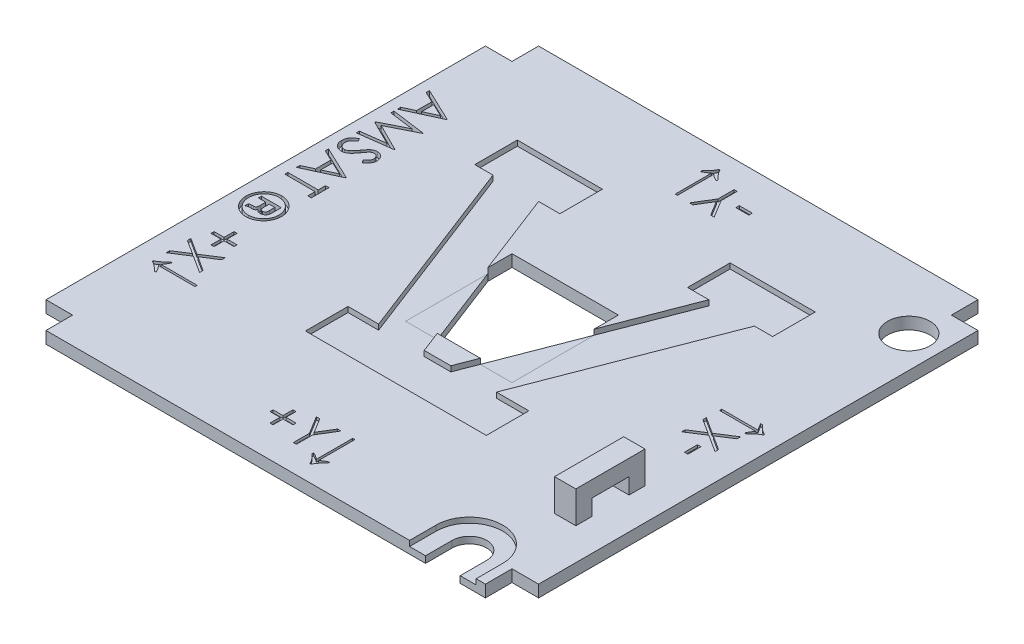
SolidWorks part; units mm, degrees
ref_plane "Front" through (0, 0, 0) normal (0, 0, 1) x (1, 0, 0)
ref_plane "Top" through (0, 0, 0) normal (0, 1, 0) x (1, 0, 0)
ref_plane "Right" through (0, 0, 0) normal (1, 0, 0) x (0, 0, -1)
sketch "Sketch2" plane through (0, 0, 0) normal (0, 1, 0) x (1, 0, 0)
  line L1 (-46.3, 41.3) -> (46.3, 41.3)
  line L2 (-46.3, 41.3) -> (-46.3, -41.3)
  line L3 (-46.3, -41.3) -> (46.3, -41.3)
  line L4 (46.3, 41.3) -> (46.3, -41.3)
  line L5 (-46.3, 41.3) -> (46.3, -41.3) construction
  line L6 (-46.3, -41.3) -> (46.3, 41.3) construction
  line L7 (-41.3, 46.3) -> (41.3, 46.3)
  line L8 (-41.3, 46.3) -> (-41.3, -46.3)
  line L9 (-41.3, -46.3) -> (41.3, -46.3)
  line L10 (41.3, 46.3) -> (41.3, -46.3)
  line L11 (-41.3, 46.3) -> (41.3, -46.3) construction
  line L12 (-41.3, -46.3) -> (41.3, 46.3) construction
  point P0 (0, 0)
  point P6 (0, 0)
  dimension "D1" = 82.6
  dimension "D2" = 92.6
  dimension "D3" = 92.6
  dimension "D4" = 82.6
extrude "Boss-Extrude1" add sketch "Sketch2" along normal blind 2.25 contours L8 L1 L2 L3 | L10 L1 L8 L3 | L10 L3 L8 L9 | L1 L10 L3 L4 | L10 L7 L8 L1 region at (-43.8, 0, 0) region at (0, 0, -43.8) region at (0, 0, 0) region at (43.8, 0, 0) region at (0, 0, 43.8)
sketch "Sketch4" plane through (0, 2.25, 0) normal (0, 1, 0) x (1, 0, 0)
  line L1 (-38.2288, 21.7712) -> (-18.2288, 21.7712)
  line L2 (-38.2288, 21.7712) -> (-38.2288, -8.2288)
  line L3 (-38.2288, -8.2288) -> (-18.2288, -8.2288)
  line L4 (-18.2288, 21.7712) -> (-18.2288, -8.2288)
  line L5 (-8.2288, 38.2288) -> (21.7712, 38.2288)
  line L6 (-8.2288, 38.2288) -> (-8.2288, 18.2288)
  line L7 (-8.2288, 18.2288) -> (21.7712, 18.2288)
  line L8 (21.7712, 38.2288) -> (21.7712, 18.2288)
  line L9 (38.2288, -21.7712) -> (18.2288, -21.7712)
  line L10 (38.2288, -21.7712) -> (38.2288, 8.2288)
  line L11 (38.2288, 8.2288) -> (18.2288, 8.2288)
  line L12 (18.2288, -21.7712) -> (18.2288, 8.2288)
  line L13 (8.2288, -18.2288) -> (-21.7712, -18.2288)
  line L14 (8.2288, -18.2288) -> (8.2288, -38.2288)
  line L15 (8.2288, -38.2288) -> (-21.7712, -38.2288)
  line L16 (-21.7712, -18.2288) -> (-21.7712, -38.2288)
  circle A0 centre (0, 0) radius 20 construction
  dimension "D11" = 40
  dimension "D1" = 20
  dimension "D2" = 30
  dimension "D3" = 10
  dimension "D4" = 30
  dimension "D5" = 20
  dimension "D6" = 30
  dimension "D7" = 20
  dimension "D8" = 30
  dimension "D9" = 20
  dimension "D10" = 10
  dimension "D12" = 10
  dimension "D13" = 10
extrude "Cut-Extrude2" [suppressed] cut sketch "Sketch4" against normal blind 10
sketch "Sketch5" plane through (0, 2.25, 0) normal (0, 1, 0) x (1, 0, 0)
  line L0 (30.05, -41.3) -> (30.05, -46.3)
  line L1 (-41.3, -46.3) -> (41.3, -46.3) construction
  line L2 (30.05, -46.3) -> (36.55, -46.3)
  line L3 (36.55, -46.3) -> (36.55, -41.3)
  line L4 (46.3, 41.3) -> (46.3, -41.3) construction
  arc A0 (30.05, -41.3) -> (36.55, -41.3) centre (33.3, -41.3) cw
  dimension "D1" = 5
  dimension "D2" = 3.25
  dimension "D3" = 13
extrude "Cut-Extrude3" cut sketch "Sketch5" against normal blind 10
sketch "Sketch6" plane through (0, 2.25, 0) normal (0, 1, 0) x (1, 0, 0)
  line L0 (27.05, -46.3) -> (27.05, -41.3)
  line L1 (-41.3, -46.3) -> (30.05, -46.3) construction
  line L2 (39.55, -46.3) -> (39.55, -41.3)
  line L4 (27.05, -41.3) -> (30.05, -41.3) construction
  line L5 (36.55, -46.3) -> (41.3, -46.3) construction
  line L8 (36.55, -46.3) -> (36.55, -41.3) construction
  line L9 (39.55, -41.3) -> (36.55, -41.3) construction
  line L10 (27.05, -46.3) -> (30.05, -46.3)
  line L11 (30.05, -46.3) -> (30.05, -41.3)
  line L12 (30.05, -41.3) -> (36.55, -41.3)
  line L13 (36.55, -41.3) -> (36.55, -46.3)
  line L14 (36.55, -46.3) -> (39.55, -46.3)
  arc A0 (27.05, -41.3) -> (39.55, -41.3) centre (33.3, -41.3) cw
  point P13 (39.55, -43.8)
  dimension "D3" = 6.25
  dimension "D1" = 3
  dimension "D2" = 3
extrude "Cut-Extrude4" cut sketch "Sketch6" against normal blind 1
sketch "Sketch7" plane through (0, 2.25, 0) normal (0, 1, 0) x (1, 0, 0)
  line L1 (-10, 10) -> (10, 10)
  line L2 (-10, 10) -> (-10, -10)
  line L3 (-10, -10) -> (10, -10)
  line L4 (10, 10) -> (10, -10)
  line L5 (-10, 10) -> (10, -10) construction
  line L6 (-10, -10) -> (10, 10) construction
  point P0 (0, 0)
  dimension "D1" = 20
  dimension "D2" = 20
extrude "Cut-Extrude5" cut sketch "Sketch7" against normal blind 10
sketch "Sketch9" [suppressed] plane through (0, 2.25, 0) normal (0, 1, 0) x (1, 0, 0)
  line L0 (-38.2288, -8.2288) -> (-18.2288, -8.2288) construction
  line L1 (-38.2288, 21.7712) -> (-31.2481, 21.7712)
  line L2 (-38.2288, 21.7712) -> (-38.2288, -8.2288)
  line L3 (-38.2288, -8.2288) -> (-31.2481, -8.2288)
  line L4 (-31.2481, 21.7712) -> (-31.2481, -8.2288)
extrude "Boss-Extrude2" [suppressed] add sketch "Sketch9" against normal blind 2.25
sketch "Sketch12" plane through (0, 2.25, 0) normal (0, 1, 0) x (1, 0, 0)
  line L1 (-44.3, 29.112) -> (-44.3, -7.0645) construction
  line L2 (-46.3, 41.3) -> (-46.3, -41.3) construction
  text T0 "AMSAT"
  dimension "D1" = 2
extrude "Cut-Extrude9" cut sketch "Sketch12" against normal blind 1
sketch "Sketch18" plane through (0, 2.25, 0) normal (0, 1, 0) x (1, 0, 0)
  line L0 (-24.5745, 21) -> (-11.0745, -14)
  line L1 (-28, 29) -> (-12, 29)
  line L2 (-28, 29) -> (-28, 21)
  line L3 (-28, 21) -> (-12, 21)
  line L4 (-12, 29) -> (-12, 21)
  line L5 (12, 29) -> (28, 29)
  line L6 (12, 29) -> (12, 21)
  line L7 (12, 21) -> (28, 21)
  line L8 (28, 29) -> (28, 21)
  line L9 (-16.8241, -14) -> (17.1759, -14)
  line L10 (-16.8241, -14) -> (-16.8241, -22)
  line L11 (-16.8241, -22) -> (17.1759, -22)
  line L12 (17.1759, -14) -> (17.1759, -22)
  line L13 (-11.0745, -14) -> (-2.5, -14)
  line L14 (-2.5, -14) -> (-16, 21)
  line L15 (2.5, -14) -> (16, 21)
  line L16 (24.5745, 21) -> (11.0745, -14)
  line L17 (0, 0) -> (0, -14) construction
  line L18 (-24.5745, 21) -> (-16, 21) construction
  line L19 (-10, -10) -> (10, -10) construction
  line L20 (16, 21) -> (24.5745, 21) construction
  point P25 (20, 21)
  dimension "D1" = 8
  dimension "D2" = 8
  dimension "D3" = 2.5
  dimension "D4" = 2.5
  dimension "D5" = 34
  dimension "D6" = 8
  dimension "D7" = 8
  dimension "D8" = 8
  dimension "D9" = 16
  dimension "D10" = 16
  dimension "D11" = 35
  dimension "D12" = 4
  dimension "D13" = 12
  dimension "D14" = 12
  dimension "D15" = 4
  dimension "D16" = 4
sketch "Sketch21" plane through (0, 2.25, 0) normal (0, 1, 0) x (1, 0, 0)
  line L0 (-44.3, 28.7864) -> (-44.3, -17.5036) construction
  line L1 (-44.3, -2.3211) -> (-37.9588, -2.3211) construction
  line L2 (-44.3, -2.3211) -> (-44.3, -24.4995) construction
  line L3 (-39.1712, -4.1935) -> (-39.1712, -5.7759)
  line L4 (-41.8971, -7.1243) -> (-42.3194, -7.1243)
  line L5 (-42.8168, -7.2909) -> (-42.916, -7.3685)
  line L6 (-42.916, -7.3685) -> (-42.916, -6.6358)
  line L7 (-42.4276, -6.5747) -> (-42.0205, -6.5544)
  line L8 (-41.5321, -5.7696) -> (-41.5321, -4.7634)
  line L9 (-41.5321, -4.7634) -> (-42.916, -4.7634)
  line L10 (-42.916, -4.7634) -> (-42.916, -4.1935)
  line L11 (-42.916, -4.1935) -> (-39.1712, -4.1935)
  line L12 (-39.8224, -4.7634) -> (-40.8808, -4.7634)
  line L13 (-40.8808, -4.7634) -> (-40.8808, -5.7288)
  line L14 (-39.8224, -5.767) -> (-39.8224, -4.7634)
  spline S0 degree 3 poles (-41.0372, -8.9967) (-41.185, -8.9949) (-41.4059, -8.984) (-41.695, -8.9354) (-41.9066, -8.8858) (-42.1141, -8.8224) (-42.3174, -8.7439) (-42.517, -8.6528) (-42.7113, -8.5469) (-42.8987, -8.4297) (-43.0761, -8.3001) (-43.2448, -8.1618) (-43.4023, -8.0112) (-43.5504, -7.8507) (-43.6877, -7.6793) (-43.8172, -7.499) (-43.9327, -7.3071) (-44.0386, -7.1097) (-44.1298, -6.9072) (-44.2087, -6.7017) (-44.27, -6.4915) (-44.3201, -6.2789) (-44.3686, -5.9894) (-44.3797, -5.7685) (-44.3814, -5.6207) knots 0 0 0 0 0.084082 0.125371 0.166472 0.207567 0.248614 0.290246 0.3322 0.374331 0.415745 0.457006 0.498264 0.539545 0.581027 0.623028 0.665647 0.708239 0.750309 0.791807 0.833294 0.874629 0.915918 1 1 1 1
  spline S1 degree 3 poles (-44.3814, -5.6207) (-44.3796, -5.473) (-44.3688, -5.2515) (-44.3197, -4.9619) (-44.2724, -4.7485) (-44.2073, -4.5397) (-44.132, -4.3329) (-44.0394, -4.1309) (-43.9357, -3.9326) (-43.8194, -3.7417) (-43.6918, -3.56) (-43.5527, -3.39) (-43.405, -3.2288) (-43.2468, -3.0786) (-43.0789, -2.9382) (-42.9, -2.8096) (-42.7123, -2.6922) (-42.5189, -2.5849) (-42.3193, -2.4938) (-42.1173, -2.4139) (-41.9108, -2.3508) (-41.7014, -2.3009) (-41.4165, -2.2526) (-41.199, -2.2413) (-41.0538, -2.2397) knots 0 0 0 0 0.084269 0.125889 0.167262 0.208679 0.250411 0.292575 0.335148 0.377862 0.419817 0.461544 0.502916 0.544266 0.585774 0.627475 0.6697 0.711864 0.753369 0.794595 0.83555 0.876272 0.917177 1 1 1 1
  spline S2 degree 3 poles (-41.0538, -2.2397) (-40.9072, -2.2412) (-40.6876, -2.2528) (-40.4002, -2.3007) (-40.1891, -2.3508) (-39.981, -2.4142) (-39.777, -2.4935) (-39.5756, -2.5852) (-39.38, -2.6921) (-39.1899, -2.8092) (-39.0095, -2.9382) (-38.8408, -3.0786) (-38.6806, -3.2276) (-38.5319, -3.388) (-38.3938, -3.5593) (-38.2673, -3.7414) (-38.1498, -3.9315) (-38.0469, -4.1294) (-37.9537, -4.3306) (-37.8781, -4.5369) (-37.8155, -4.7468) (-37.7653, -4.9599) (-37.7203, -5.2511) (-37.704, -5.4722) (-37.7058, -5.6207) knots 0 0 0 0 0.083231 0.124457 0.16526 0.206291 0.24781 0.289377 0.331805 0.374278 0.416018 0.457555 0.498758 0.540138 0.581556 0.62355 0.665898 0.708311 0.750097 0.791671 0.832863 0.874368 0.915793 1 1 1 1
  spline S3 degree 3 poles (-37.7058, -5.6207) (-37.7041, -5.7692) (-37.7201, -5.9904) (-37.7656, -6.281) (-37.8141, -6.4939) (-37.8766, -6.703) (-37.9531, -6.9082) (-38.0436, -7.1096) (-38.1476, -7.3057) (-38.2632, -7.4954) (-38.39, -7.6758) (-38.5281, -7.8455) (-38.6763, -8.0054) (-38.8353, -8.1553) (-39.0044, -8.2956) (-39.1852, -8.4244) (-39.3744, -8.5433) (-39.571, -8.6495) (-39.7707, -8.743) (-39.974, -8.8209) (-40.1807, -8.8842) (-40.3903, -8.9357) (-40.6754, -8.9835) (-40.8923, -8.9953) (-41.0372, -8.9967) knots 0 0 0 0 0.084514 0.12609 0.167457 0.208799 0.250299 0.292137 0.334491 0.376661 0.41861 0.459992 0.501181 0.542701 0.584388 0.62628 0.669037 0.711619 0.753439 0.794572 0.835522 0.876529 0.917429 1 1 1 1
  spline S4 degree 3 poles (-41.0436, -8.5082) (-40.9191, -8.5073) (-40.7328, -8.4969) (-40.4891, -8.4555) (-40.3097, -8.4134) (-40.1331, -8.359) (-39.9597, -8.2909) (-39.789, -8.2118) (-39.6215, -8.1223) (-39.4605, -8.0203) (-39.307, -7.9101) (-39.1618, -7.7914) (-39.0277, -7.662) (-38.8994, -7.5267) (-38.7831, -7.3804) (-38.6722, -7.2281) (-38.5746, -7.0654) (-38.4851, -6.898) (-38.4079, -6.7262) (-38.3408, -6.5515) (-38.2878, -6.3727) (-38.2454, -6.191) (-38.2067, -5.9431) (-38.1945, -5.7546) (-38.1942, -5.6284) knots 0 0 0 0 0.083087 0.124099 0.164782 0.205936 0.24722 0.288982 0.331375 0.373829 0.415981 0.457375 0.498787 0.540211 0.581645 0.623403 0.665799 0.70806 0.74996 0.791407 0.832749 0.874259 0.915784 1 1 1 1
  spline S5 degree 3 poles (-38.1942, -5.6284) (-38.1944, -5.5012) (-38.2068, -5.3115) (-38.2452, -5.0623) (-38.288, -4.8798) (-38.341, -4.6998) (-38.4078, -4.5229) (-38.4851, -4.3486) (-38.5745, -4.1786) (-38.6722, -4.0134) (-38.7831, -3.8586) (-38.8991, -3.7098) (-39.0273, -3.573) (-39.1623, -3.4439) (-39.3061, -3.3234) (-39.461, -3.2151) (-39.6214, -3.1127) (-39.7891, -3.0235) (-39.9597, -2.9435) (-40.1344, -2.878) (-40.3116, -2.8224) (-40.4925, -2.7811) (-40.7387, -2.7392) (-40.9267, -2.7291) (-41.0525, -2.7281) knots 0 0 0 0 0.084266 0.125816 0.167074 0.208434 0.250155 0.292315 0.334816 0.377436 0.419398 0.46102 0.502398 0.543559 0.58488 0.626613 0.668809 0.710945 0.752453 0.793648 0.834552 0.875536 0.916576 1 1 1 1
  spline S6 degree 3 poles (-41.0525, -2.7281) (-41.1774, -2.7291) (-41.3641, -2.7393) (-41.6082, -2.7809) (-41.7874, -2.8226) (-41.963, -2.878) (-42.1364, -2.9435) (-42.3058, -3.0235) (-42.4721, -3.1128) (-42.6312, -3.2146) (-42.7838, -3.3243) (-42.9273, -3.4435) (-43.0617, -3.573) (-43.1872, -3.7114) (-43.305, -3.8587) (-43.4144, -4.0147) (-43.5132, -4.18) (-43.6014, -4.3506) (-43.6797, -4.5245) (-43.7461, -4.7011) (-43.7994, -4.8814) (-43.8416, -5.064) (-43.8807, -5.3127) (-43.8926, -5.5017) (-43.8929, -5.6284) knots 0 0 0 0 0.083161 0.124071 0.164652 0.205433 0.246513 0.287914 0.329953 0.372063 0.413487 0.454957 0.496062 0.537606 0.579157 0.621501 0.664274 0.707178 0.749231 0.791103 0.832611 0.874292 0.915713 1 1 1 1
  spline S7 degree 3 poles (-43.8929, -5.6284) (-43.8929, -5.7543) (-43.8801, -5.9421) (-43.8424, -6.1896) (-43.7975, -6.3704) (-43.745, -6.5493) (-43.6783, -6.7246) (-43.6005, -6.8972) (-43.5107, -7.0654) (-43.4099, -7.2275) (-43.3028, -7.3836) (-43.1836, -7.5283) (-43.0571, -7.6647) (-42.9241, -7.794) (-42.7803, -7.9121) (-42.6295, -8.0235) (-42.4693, -8.1228) (-42.3041, -8.2137) (-42.1344, -8.2921) (-41.9611, -8.3589) (-41.7848, -8.4137) (-41.604, -8.4556) (-41.3577, -8.4967) (-41.1694, -8.5076) (-41.0436, -8.5082) knots 0 0 0 0 0.083922 0.125442 0.166735 0.208071 0.249777 0.291673 0.33431 0.376848 0.418899 0.460506 0.501732 0.542934 0.584104 0.625793 0.667851 0.709742 0.751498 0.792411 0.833559 0.874512 0.916077 1 1 1 1
  spline S8 degree 3 poles (-39.1712, -5.7759) (-39.1708, -5.862) (-39.1733, -5.9864) (-39.1852, -6.1455) (-39.1983, -6.2502) (-39.2129, -6.3455) (-39.2316, -6.431) (-39.2548, -6.5064) (-39.2878, -6.5944) (-39.3428, -6.6921) (-39.4239, -6.7982) (-39.5231, -6.8928) (-39.6383, -6.9754) (-39.7682, -7.0407) (-39.9595, -7.1088) (-40.115, -7.1221) (-40.2193, -7.1243) knots 0 0 0 0 0.131786 0.190365 0.24397 0.293257 0.337811 0.377839 0.413992 0.48137 0.548473 0.617773 0.690341 0.764636 0.839543 1 1 1 1
  spline S9 degree 3 poles (-40.2193, -7.1243) (-40.3084, -7.1267) (-40.4743, -7.1117) (-40.6384, -7.082) (-40.7116, -7.0556) knots 0 0 0 0 0.534352 1 1 1 1
  spline S10 degree 3 poles (-40.7116, -7.0556) (-40.7738, -7.0206) (-40.8956, -6.9017) (-40.9959, -6.7655) (-41.0474, -6.6816) knots 0 0 0 0 0.418044 1 1 1 1
  spline S11 degree 3 poles (-41.0474, -6.6816) (-41.0832, -6.7597) (-41.1465, -6.8646) (-41.2512, -6.9786) (-41.3362, -7.0387) (-41.4395, -7.0787) (-41.6269, -7.1176) (-41.7836, -7.1254) (-41.8971, -7.1243) knots 0 0 0 0 0.248758 0.352185 0.446606 0.54746 0.670874 1 1 1 1
  spline S12 degree 3 poles (-42.3194, -7.1243) (-42.412, -7.123) (-42.5915, -7.1489) (-42.751, -7.2354) (-42.8168, -7.2909) knots 0 0 0 0 0.518993 1 1 1 1
  spline S13 degree 3 poles (-42.916, -6.6358) (-42.8417, -6.6196) (-42.6791, -6.5953) (-42.5156, -6.5795) (-42.4276, -6.5747) knots 0 0 0 0 0.463214 1 1 1 1
  spline S14 degree 3 poles (-42.0205, -6.5544) (-41.9567, -6.5474) (-41.8665, -6.5384) (-41.762, -6.5022) (-41.7047, -6.4705) (-41.6609, -6.4305) (-41.6229, -6.3858) (-41.5938, -6.3323) (-41.5693, -6.2685) (-41.5517, -6.1846) (-41.5345, -6.0164) (-41.5323, -5.8743) (-41.5321, -5.7696) knots 0 0 0 0 0.179641 0.249904 0.307061 0.360638 0.414345 0.469893 0.529361 0.604464 0.707939 1 1 1 1
  spline S15 degree 3 poles (-40.8808, -5.7288) (-40.8825, -5.852) (-40.872, -6.054) (-40.8293, -6.2537) (-40.7905, -6.3242) knots 0 0 0 0 0.607223 1 1 1 1
  spline S16 degree 3 poles (-40.7905, -6.3242) (-40.7508, -6.398) (-40.6185, -6.5247) (-40.4384, -6.5558) (-40.3478, -6.5544) knots 0 0 0 0 0.477173 1 1 1 1
  spline S17 degree 3 poles (-40.3478, -6.5544) (-40.2679, -6.5558) (-40.1514, -6.538) (-40.0196, -6.4657) (-39.9569, -6.4036) (-39.9185, -6.3418) (-39.8911, -6.2869) (-39.8708, -6.2218) (-39.8525, -6.1484) (-39.8392, -6.0658) (-39.8246, -5.9379) (-39.8243, -5.8369) (-39.8224, -5.767) knots 0 0 0 0 0.220304 0.315334 0.409336 0.459153 0.514956 0.577646 0.646091 0.722966 0.807444 1 1 1 1
extrude "Cut-Extrude10" cut sketch "Sketch21" against normal blind 1 contours S14 L7 S13 L6 L5 S12 L4 S11 S10 S9 S8 L3 L11 L10 L9 L8 S17 S16 S15 L13 L12 L14 | S3 S2 S1 S0 S7 S6 S5 S4 region at (-39.2203, 2.25, 4.9847) region at (-43.3391, 2.25, 7.9367)
extrude "Cut-Extrude7" cut sketch "Sketch18" against normal blind 1 contours L9 L14 L3 L0 | L16 L7 L15 L9 | L4 L1 L2 L3 | L8 L5 L6 L7 | L12 L9 L10 L11 region at (-13.5372, 2.25, -3.5) region at (-20, 2.25, -25) region at (0.1759, 2.25, 18) region at (13.5372, 2.25, -3.5) region at (20, 2.25, -25)
sketch "Sketch19" plane through (0, 2.25, 0) normal (0, 1, 0) x (1, 0, 0)
  line L0 (-10, 5.4444) -> (-4.0429, -10)
  line L1 (-4.0429, -10) -> (4.0429, -10) construction
  line L2 (-2.5, -14) -> (-4.0429, -10) construction
  line L4 (4.0429, -10) -> (10, 5.4444)
  line L5 (10, 5.4444) -> (10, -10)
  line L6 (10, 5.4444) -> (10, -10) construction
  line L7 (10, -10) -> (4.0429, -10) construction
  line L8 (10, -10) -> (-10, -10)
  line L9 (-10, -10) -> (-10, 5.4444)
extrude "Boss-Extrude3" add sketch "Sketch19" against normal blind 2.25 separate body contours L9 L8 L0 | L8 L5 L4 region at (8.0143, 2.25, 4.8519) region at (-8.0143, 2.25, 4.8519)
sketch "Sketch20" plane through (0, 2.25, 0) normal (0, 1, 0) x (1, 0, 0)
  line L0 (-10, 5.4444) -> (-10, -10)
  line L1 (-10, -10) -> (-4.0429, -10)
  line L2 (-4.0429, -10) -> (-10, 5.4444)
  line L3 (4.0429, -10) -> (10, 5.4444)
  line L4 (10, 5.4444) -> (10, -10)
  line L5 (10, -10) -> (4.0429, -10)
extrude "Cut-Extrude8" cut sketch "Sketch20" against normal blind 1
sketch "Sketch22" plane through (0, 2.25, 0) normal (0, 1, 0) x (1, 0, 0)
  line L0 (-46.3, -41.3) -> (46.3, -41.3) construction
  line L1 (-46.3, 41.3) -> (-46.3, -41.3) construction
  line L2 (46.3, 41.3) -> (46.3, -41.3) construction
  line L3 (-36.3, -46.3) -> (-36.3, 46.3) construction
  line L4 (-41.3, -46.3) -> (27.05, -46.3) construction
  line L5 (-41.3, 46.3) -> (41.3, 46.3) construction
  line L6 (-46.3, 41.3) -> (46.3, 41.3) construction
  line L7 (41.3, 46.3) -> (41.3, -46.3) construction
  text T0 "↑X+                "
  text T1 "+Y↓"
  text T2 "↓Y-"
  text T3 "↓X-"
  dimension "D1" = 10
  dimension "D2" = 5
  dimension "D3" = 5
  dimension "D4" = 5
extrude "Cut-Extrude11" cut sketch "Sketch22" against normal blind 0.5
sketch "Sketch23" plane through (0, 2.25, 0) normal (0, 1, 0) x (1, 0, 0)
  line L0 (-41.3, -46.3) -> (27.05, -46.3) construction
  line L1 (36.3, -15.3) -> (40.3, -15.3)
  line L2 (36.3, -15.3) -> (36.3, -18.3)
  line L3 (36.3, -18.3) -> (40.3, -18.3)
  line L4 (40.3, -15.3) -> (40.3, -18.3)
  line L5 (36.3, -25.3) -> (40.3, -25.3)
  line L6 (36.3, -25.3) -> (36.3, -28.3)
  line L7 (36.3, -28.3) -> (40.3, -28.3)
  line L8 (40.3, -25.3) -> (40.3, -28.3)
  line L9 (46.3, 41.3) -> (46.3, -41.3) construction
  line L10 (36.3, -18.3) -> (36.3, -25.3) construction
  point P10 (40.3, -16.8)
  dimension "D1" = 7
  dimension "D2" = 3
  dimension "D3" = 3
  dimension "D4" = 4
  dimension "D5" = 4
  dimension "D6" = 18
  dimension "D7" = 6
extrude "Boss-Extrude4" add sketch "Sketch23" along normal blind 3
sketch "Sketch24" plane through (0, 5.25, 0) normal (0, 1, 0) x (1, 0, 0)
  line L1 (36.3, -15.3) -> (40.3, -15.3)
  line L2 (36.3, -15.3) -> (36.3, -28.3)
  line L3 (36.3, -28.3) -> (40.3, -28.3)
  line L4 (40.3, -15.3) -> (40.3, -28.3)
extrude "Boss-Extrude5" add sketch "Sketch24" along normal blind 3
sketch "Sketch3" plane through (0, 2.25, 0) normal (0, 1, 0) x (1, 0, 0)
  line L0 (-41.3, 46.3) -> (41.3, 46.3) construction
  line L2 (46.3, 41.3) -> (46.3, -41.3) construction
  circle A1 centre (40.3, 34.3) radius 4
  dimension "D2" = 8
  dimension "D5" = 12
  dimension "D6" = 6
extrude "Cut-Extrude1" cut sketch "Sketch3" against normal blind 10
